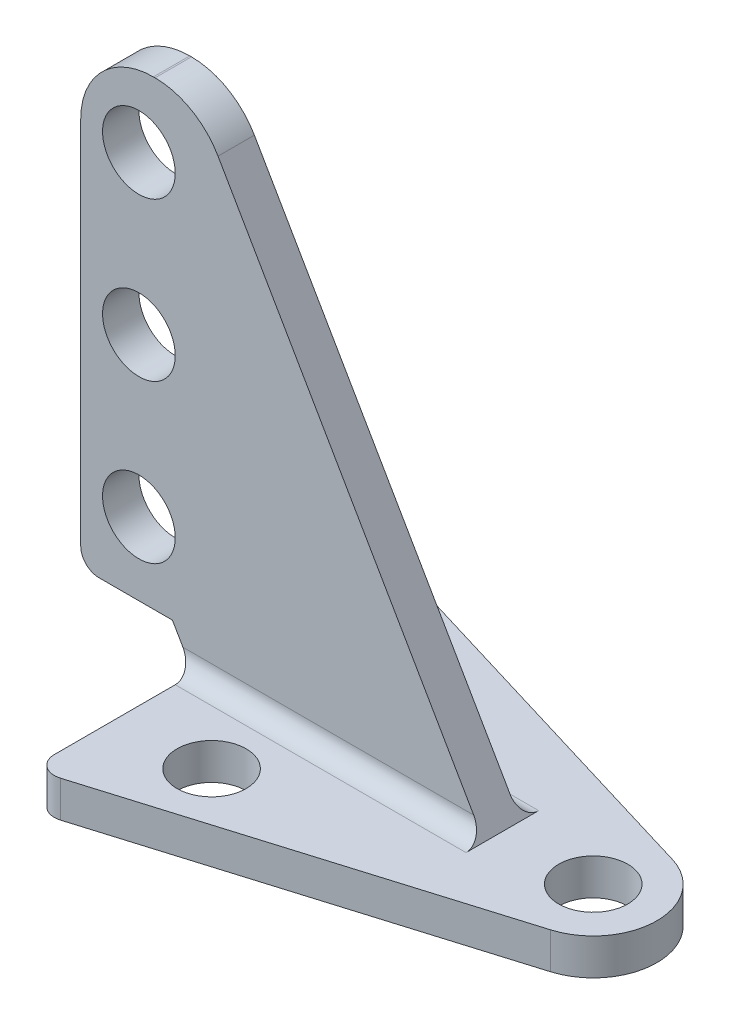
SolidWorks part; units mm, degrees
ref_plane "Ön Düzlem" through (0, 0, 0) normal (0, 0, 1) x (1, 0, 0)
ref_plane "Üst Düzlem" through (0, 0, 0) normal (0, 1, 0) x (1, 0, 0)
ref_plane "Sağ Düzlem" through (0, 0, 0) normal (1, 0, 0) x (0, 0, -1)
sketch "Çizim1" plane through (0, 0, 0) normal (0, 1, 0) x (1, 0, 0)
  line L0 (0, -2.5) -> (0, 2.5) construction
  line L1 (0, 0) -> (8, 0) construction
  line L2 (-2.5, 5) -> (-2.5, -5)
  line L3 (-2.5, -5) -> (8.5061, -1.6752)
  line L4 (8.5061, 1.6752) -> (-2.5, 5)
  circle A0 centre (0, 2.5) radius 0.95
  circle A1 centre (0, -2.5) radius 0.95
  circle A2 centre (8, 0) radius 0.95
  arc A4 (8.5061, -1.6752) -> (8.5061, 1.6752) centre (8, 0) ccw
  point P3 (0.5752, -4.2492)
  point P4 (0, 0)
  point P12 (-1.7852, 4.8688)
  point P13 (-2.1469, -5.5056)
  point P17 (-2.3944, -2.5)
  point P18 (-2.3373, -5)
  point P19 (-2.5, 0)
  point P20 (0, 0)
  point P21 (-1.3265, -2.1633)
  point P22 (0.2801, 3.5474)
  point P23 (0, 0)
  point P24 (-2.0137, -2.5)
  point P25 (-1.633, 2.5)
  point P26 (0, 0)
  point P27 (-1.8804, 2.5)
  dimension "D3" = 1.9
  dimension "D4" = 0.8
  dimension "D1" = 5
  dimension "D2" = 8
  dimension "D5" = 10
  dimension "D6" = 2.5
extrude "Yükseklik-Ekstrüzyon1" add sketch "Çizim1" along normal blind 1
fillet "Radyus1" radius 0.5 2 edges at (-2.5, 0.5, -5) (-2.5, 0.5, 5)
sketch "Çizim2" plane through (0, 0, 0) normal (0, 0, 1) x (1, 0, 0)
  line L0 (-4, 4) -> (-4, 12.6832) construction
  line L1 (-2.5, 1) -> (-3.0774, 2)
  line L2 (-3.0774, 2) -> (-5.6, 2)
  line L3 (-5.6, 2) -> (-5.6, 14.6832)
  line L4 (-5.6, 14.6832) -> (-2.4, 14.6832)
  line L5 (-2.4, 14.6832) -> (5.5, 1)
  line L6 (-1.8554, 1) -> (8.5061, 1) construction
  line L7 (-2.5, 1) -> (5.5, 1)
  circle A0 centre (-4, 4) radius 1
  circle A1 centre (-4, 12.6832) radius 1
  circle A2 centre (-4, 8.3416) radius 1
  point P7 (-2.5, 15.1436)
  point P17 (0, 0)
  point P18 (-5.6, 8.3416)
  point P19 (-5.8119, 15.3966)
  point P20 (-4, 14.6832)
  point P21 (-4, 12.478)
  point P22 (-4, 12.7346)
  dimension "D2" = 2
  dimension "D1" = 4
  dimension "D3" = 60
  dimension "D4" = 3.2
  dimension "D5" = 8
  dimension "D6" = 1
  dimension "D7" = 2
extrude "Yükseklik-Ekstrüzyon2" add sketch "Çizim2" along normal mid plane 1
fillet "Radyus2" radius 0.5 3 edges at (-5.6, 2, 0) (1.5, 1, -0.5) (1.5, 1, 0.5)
fillet "Radyus3" radius 2 2 edges at (-2.4, 14.6832, 0) (-5.6, 14.6832, 0)
